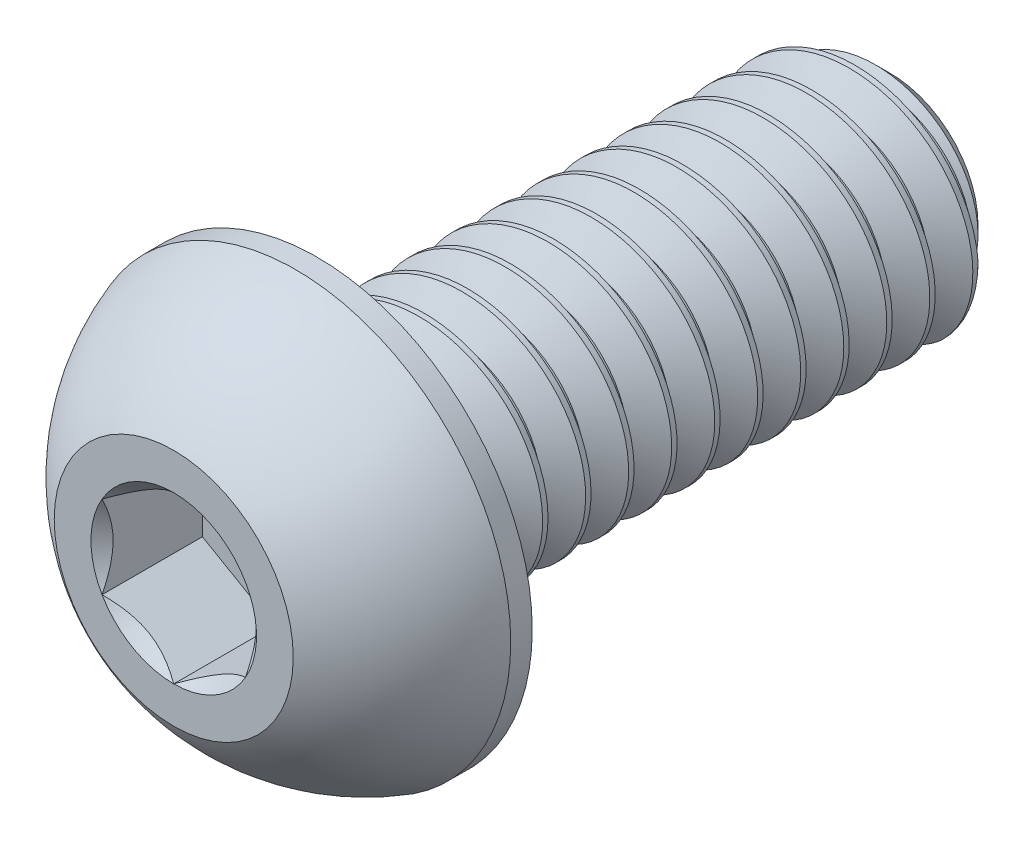
SolidWorks part; units mm, degrees
material "Alloy Steel (SS)"
ref_plane "Front" through (0, 0, 0) normal (0, 0, 1) x (1, 0, 0)
ref_plane "Top" through (0, 0, 0) normal (0, 1, 0) x (1, 0, 0)
ref_plane "Right" through (0, 0, 0) normal (1, 0, 0) x (0, 0, -1)
sketch "Sketch1" plane through (0, 0, 0) normal (1, 0, 0) x (0, 0, -1)
  line L2 (1.5, 1.25) -> (7.5, 1.25)
  line L3 (7.5, 1.25) -> (7.5, 0)
  line L4 (7.5, 0) -> (1.5, 0)
  line L6 (1.275, 2.25) -> (1.5, 2.25) construction
  line L7 (7.5, 1.25) -> (7.5, -1.25) construction
  line L8 (0, 0) -> (1.5, 0) construction
  line L9 (1.5, 2.25) -> (1.5, -2.25) construction
  line L11 (1.5, 1.25) -> (1.5, 0)
  line L13 (0, 0.75) -> (0, -0.75) construction
  line L14 (0, 0.75) -> (0, 1.25) construction
  line L15 (7.4719, 1.2987) -> (7.6969, 0.909) construction
  line L16 (7.6969, 0.909) -> (7.9219, 1.2987) construction
  line L17 (7.9219, 1.2987) -> (7.4719, 1.2987) construction
  line L18 (7.5, 1.25) -> (7.8938, 1.25) construction
  line L19 (7.6969, 1.2987) -> (7.6969, 1.25) construction
  line L20 (7.6969, 1.25) -> (7.6969, 0.9577) construction
  line L21 (7.6969, 0.9577) -> (7.6969, 0.909) construction
  line L22 (7.6688, 0.9577) -> (7.725, 0.9577)
  line L23 (7.4859, 1.2744) -> (7.9078, 1.2744)
  line L24 (7.725, 0.9577) -> (7.9078, 1.2744)
  line L25 (7.6688, 0.9577) -> (7.4859, 1.2744)
  line L26 (7.1625, 1.25) -> (7.5, 0.9125)
  arc A3 (0, 1.25) -> (1.275, 2.25) centre (2.01, 0) cw construction
  point P29 (7.6969, 1.2744)
  point P30 (6.375, -1.25)
  dimension "D1" = 0.225
  dimension "Pitch" = 0.45
  dimension "D3" = 0.0563
  dimension "D2" = 0.3375
  dimension "D4" = 45
  dimension "D5" = 1.125
sketch "Sketch10" plane through (0, 0, 0) normal (1, 0, 0) x (0, 0, -1)
  line L0 (7.1625, 1.25) -> (7.5, 0.9125) construction
  line L1 (7.1625, 1.25) -> (7.5, 0.9125)
  line L4 (7.5, 1.25) -> (1.5, 1.25)
  line L5 (7.5, 0) -> (7.5, 1.25)
  line L6 (1.5, 0) -> (7.5, 0)
  line L7 (1.5, 1.25) -> (1.5, 0)
  line L8 (7.1625, 1.25) -> (1.5, 1.25)
  line L9 (7.5, 0) -> (7.5, 0.9125)
  line L10 (1.5, 0) -> (7.5, 0)
  line L11 (1.5, 1.25) -> (1.5, 0)
  dimension "D1" = 0
revolve "Revolve3" add sketch "Sketch10" angle 360 about L8
sketch "Sketch7" plane through (0, 0, 0) normal (1, 0, 0) x (0, 0, -1)
  line L6 (1.275, 2.25) -> (1.5, 2.25) construction
  line L8 (0, 0) -> (1.5, 0) construction
  line L11 (1.5, 2.25) -> (1.5, -2.25) construction
  line L12 (1.275, 2.25) -> (1.5, 2.25)
  line L13 (0, 0) -> (1.5, 0)
  line L14 (0, 0.75) -> (0, -0.75) construction
  line L15 (1.5, 2.25) -> (1.5, 0)
  line L16 (0, 1.25) -> (0, 0)
  arc A2 (1.275, 2.25) -> (0, 1.25) centre (2.01, 0) ccw construction
  arc A3 (1.275, 2.25) -> (0, 1.25) centre (2.01, 0) ccw
revolve "Revolve2" add sketch "Sketch7" angle 360 mid plane about L13
sketch "Sketch5" plane through (0, 0, 0) normal (0, 0, 1) x (1, 0, 0)
  line L1 (0.75, -0.433) -> (0.75, 0.433)
  line L2 (0.75, 0.433) -> (0, 0.866)
  line L3 (0, 0.866) -> (-0.75, 0.433)
  line L4 (-0.75, 0.433) -> (-0.75, -0.433)
  line L5 (-0.75, -0.433) -> (0, -0.866)
  line L6 (0, -0.866) -> (0.75, -0.433)
  circle A0 centre (0, 0) radius 0.75 construction
extrude "Cut-Extrude2" cut sketch "Sketch5" against normal blind 1.05
sketch "Sketch6" plane through (0, 0, 0) normal (0, 0, 1) x (1, 0, 0)
  circle A0 centre (0, 0) radius 0.866
extrude "Cut-Extrude3" cut sketch "Sketch6" against normal blind 1.05 draft 45
sketch "Sketch9" plane through (0, 0, -1.5) normal (0, 0, -1) x (-1, 0, 0)
  circle A0 centre (0, 0) radius 1.25 construction
  circle A4 centre (0, 0) radius 1.25
split "Split1" bodies to split 113 resulting bodies 123 124 split by face at (2.25, 0, -1.5)
sketch "Sketch11" plane through (0, 0, -7.5) normal (0, 0, -1) x (-1, 0, 0)
  circle A0 centre (0, 0) radius 1.25 construction
  circle A1 centre (0, 0) radius 1.25
curve "Helix/Spiral1" pitch 0.45 height 7.5 radius 1.25 centre (0, 0, -7.5) axis (0, 0, 1) start towards (0, 1, 0)
sketch "Sketch12" plane through (0, 0, 0) normal (1, 0, 0) x (0, 0, -1)
  line L0 (7.6688, 0.9577) -> (7.725, 0.9577) construction
  line L1 (7.725, 0.9577) -> (7.9078, 1.2744) construction
  line L2 (7.4859, 1.2744) -> (7.9078, 1.2744) construction
  line L3 (7.6688, 0.9577) -> (7.4859, 1.2744) construction
  line L4 (7.6688, 0.9577) -> (7.725, 0.9577)
  line L5 (7.725, 0.9577) -> (7.9078, 1.2744)
  line L6 (7.4859, 1.2744) -> (7.9078, 1.2744)
  line L7 (7.6688, 0.9577) -> (7.4859, 1.2744)
sweep "Cut-Sweep2" cut profiles "Sketch12" path "Helix/Spiral1" align with end faces yes
extrude "Boss-Extrude1" add sketch "Sketch9" along normal blind 10 draft 45
equation "\"D1@Cut-Extrude2\" = \"Head Ht@Sketch1\" * .7"
equation "\"D1@Sketch1\" = \"Head Ht@Sketch1\" * .15"
equation "\"D1@Cut-Extrude3\" = \"D1@Cut-Extrude2\""
equation "\"D3@Sketch1\" = \"Pitch@Sketch1\" / 8"
equation "\"D2@Sketch1\"=\"Pitch@Sketch1\"*0.75"
equation "\"D3@Helix/Spiral1\" = \"Lg@Sketch1\" + \"Head Ht@Sketch1\""
equation "\"D4@Helix/Spiral1\"=\"pitch@sketch1\""
equation "\"D5@Sketch1\"=\"Pitch@Sketch1\"*2.5"
